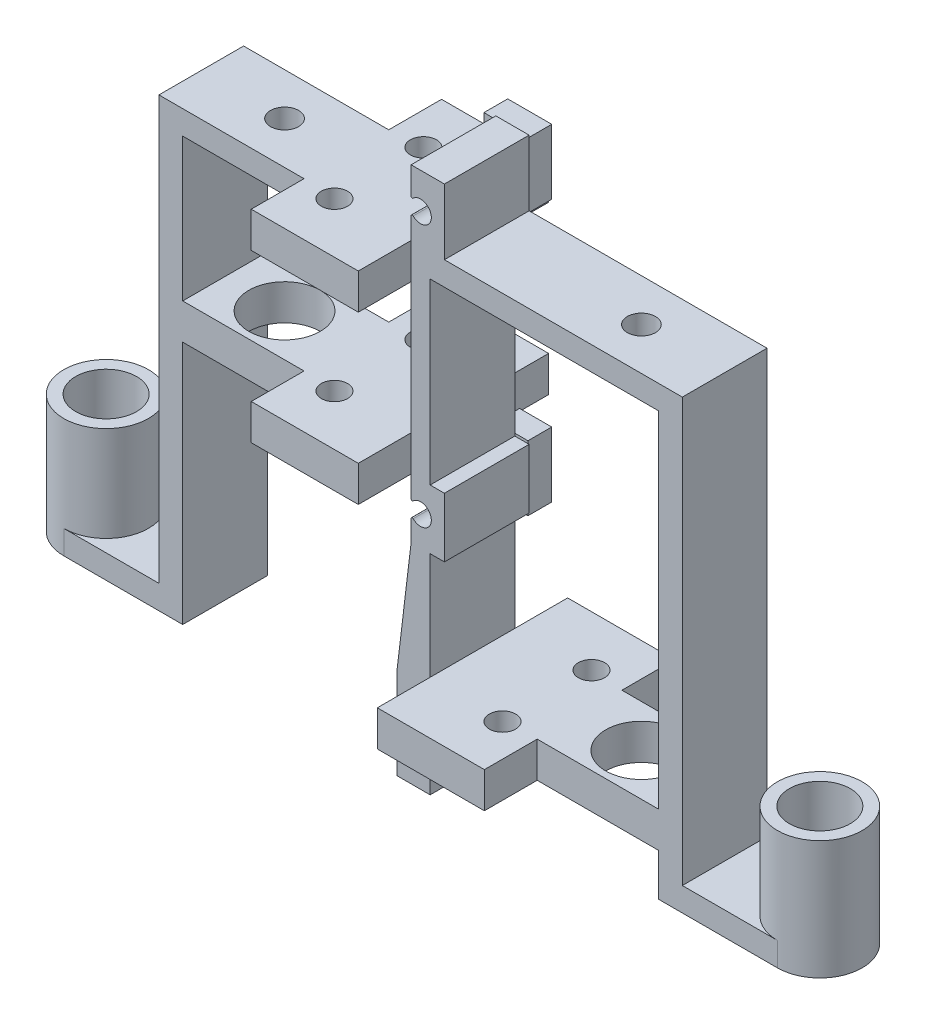
SolidWorks part; units mm, degrees
note: The reader was unsure of these and kept them because the rebuilt part matched: shared geometry of "Sketch11<3>".
material "Nylon 12 (Density Only)"
ref_plane "Front Plane" through (0, 0, 0) normal (0, 0, 1) x (1, 0, 0)
ref_plane "Top Plane" through (0, 0, 0) normal (0, 1, 0) x (1, 0, 0)
ref_plane "Right Plane" through (0, 0, 0) normal (1, 0, 0) x (0, 0, -1)
sketch "Sketch1" plane through (0, 0, 0) normal (0, 1, 0) x (1, 0, 0)
  line L0 (0, 0) -> (76.2, 0) construction
  line L1 (0, 4.5212) -> (76.2, 4.5212)
  line L2 (0, -4.5212) -> (76.2, -4.5212)
  circle A0 centre (0, 0) radius 3.2512
  circle A1 centre (76.2, 0) radius 3.2512
  arc A2 (0, 4.5212) -> (0, -4.5212) centre (0, 0) ccw
  arc A3 (76.2, -4.5212) -> (76.2, 4.5212) centre (76.2, 0) ccw
  point P5 (38.1, 0)
  point P10 (0, 3.2512)
  dimension "D1" = 76.2
  dimension "D2" = 6.5024
  dimension "D3" = 6.5024
  dimension "D4" = 1.27
extrude "Boss-Extrude1" add sketch "Sketch1" along normal blind 12.7
sketch "Sketch2" plane through (0, 12.7, 0) normal (0, 1, 0) x (1, 0, 0)
  line L2 (0, -4.5212) -> (76.2, -4.5212)
  line L3 (76.2, 4.5212) -> (0, 4.5212)
  line L4 (0, -4.5212) -> (76.2, -4.5212)
  line L5 (76.2, 4.5212) -> (0, 4.5212)
  circle A0 centre (0, 0) radius 4.5212
  circle A1 centre (0, 0) radius 3.2512
  circle A2 centre (0, 0) radius 3.2512
  circle A3 centre (76.2, 0) radius 3.2512
  circle A4 centre (76.2, 0) radius 3.2512
  circle A5 centre (76.2, 0) radius 4.5212
  arc A6 (0, 4.5212) -> (0, -4.5212) centre (0, 0) ccw
  arc A7 (76.2, -4.5212) -> (76.2, 4.5212) centre (76.2, 0) ccw
  arc A8 (0, 4.5212) -> (0, -4.5212) centre (0, 0) ccw
  arc A9 (76.2, -4.5212) -> (76.2, 4.5212) centre (76.2, 0) ccw
  dimension "D1" = 0
  dimension "D2" = 0
  dimension "D3" = 0
  dimension "D4" = 1.27
extrude "Cut-Extrude2" cut sketch "Sketch2" against normal blind 10.16 contours A5 L5 A0 L4
sketch "Sketch3" plane through (0, 2.54, 0) normal (0, 1, 0) x (1, 0, 0)
  line L0 (76.2, 4.5212) -> (0, 4.5212) construction
  line L1 (38.1, 4.5212) -> (12.7, 4.5212)
  line L2 (38.1, 4.5212) -> (38.1, -4.5212)
  line L3 (38.1, -4.5212) -> (12.7, -4.5212)
  line L4 (12.7, 4.5212) -> (12.7, -4.5212)
  line L5 (0, -4.5212) -> (76.2, -4.5212) construction
  line L7 (38.1, 4.5212) -> (63.5, 4.5212)
  line L8 (38.1, 4.5212) -> (38.1, -4.5212)
  line L9 (38.1, -4.5212) -> (63.5, -4.5212)
  line L10 (63.5, 4.5212) -> (63.5, -4.5212)
  line M4 (76.2, 4.5212) -> (0, 4.5212)
  line M6 (0, -4.5212) -> (76.2, -4.5212)
  dimension "D1" = 25.4
  dimension "D2" = 25.4
extrude "Cut-Extrude3" cut sketch "Sketch3" against normal blind 10.16 contours L4 L2 M4 M6 | L10 L2 M4 M6
sketch "Sketch4" plane through (0, 2.54, 0) normal (0, 1, 0) x (1, 0, 0)
  line L0 (0, -4.5212) -> (12.7, -4.5212) construction
  line L1 (12.7, 4.5212) -> (10.16, 4.5212)
  line L2 (12.7, 4.5212) -> (12.7, -4.5212)
  line L3 (12.7, -4.5212) -> (10.16, -4.5212)
  line L4 (10.16, 4.5212) -> (10.16, -4.5212)
  line L5 (63.5, -4.5212) -> (76.2, -4.5212) construction
  line L6 (63.5, 4.5212) -> (66.04, 4.5212)
  line L7 (63.5, 4.5212) -> (63.5, -4.5212)
  line L8 (63.5, -4.5212) -> (66.04, -4.5212)
  line L9 (66.04, 4.5212) -> (66.04, -4.5212)
  dimension "D1" = 2.54
  dimension "D2" = 2.54
extrude "Boss-Extrude2" add sketch "Sketch4" along normal blind 45.16
sketch "Sketch5" plane through (0, 47.7, 0) normal (0, 1, 0) x (1, 0, 0)
  line L0 (10.16, 4.5212) -> (66.04, -4.5212) construction
  line L1 (10.16, 4.5212) -> (66.04, 4.5212)
  line L2 (10.16, 4.5212) -> (10.16, -4.5212)
  line L3 (10.16, -4.5212) -> (66.04, -4.5212)
  line L4 (66.04, 4.5212) -> (66.04, -4.5212)
  line L5 (38.1, 0) -> (19.05, 0) construction
  line L6 (38.1, 0) -> (57.15, 0) construction
  circle A0 centre (19.05, 0) radius 1.5
  circle A1 centre (57.15, 0) radius 1.5
  dimension "D1" = 19.05
  dimension "D3" = 3
  dimension "D4" = 3
  dimension "D2" = 19.05
extrude "Boss-Extrude3" add sketch "Sketch5" against normal blind 2.54
sketch "Sketch7" plane through (0, 47.7, 0) normal (0, 1, 0) x (1, 0, 0)
  line L1 (38.1, 4.5212) -> (35.56, 4.5212)
  line L2 (38.1, 4.5212) -> (38.1, -4.5212)
  line L3 (38.1, -4.5212) -> (35.56, -4.5212)
  line L4 (10.16, -4.5212) -> (66.04, -4.5212)
  line L5 (66.04, -4.5212) -> (66.04, 4.5212)
  line L6 (66.04, 4.5212) -> (10.16, 4.5212)
  line L7 (10.16, 4.5212) -> (10.16, -4.5212)
  line L8 (10.16, -4.5212) -> (66.04, -4.5212)
  line L9 (66.04, -4.5212) -> (66.04, 4.5212)
  line L10 (66.04, 4.5212) -> (10.16, 4.5212)
  line L11 (10.16, 4.5212) -> (10.16, -4.5212)
  line L12 (35.56, 4.5212) -> (35.56, -4.5212)
  line L13 (38.1, 4.5212) -> (40.64, 4.5212)
  line L14 (38.1, 4.5212) -> (38.1, -4.5212)
  line L15 (38.1, -4.5212) -> (40.64, -4.5212)
  line L16 (40.64, 4.5212) -> (40.64, -4.5212)
  line M8 (10.16, -4.5212) -> (66.04, -4.5212)
  line M10 (66.04, 4.5212) -> (10.16, 4.5212)
  dimension "D2" = 2.54
  dimension "D3" = 2.54
  dimension "D1" = 0
extrude "Boss-Extrude4" add sketch "Sketch7" along normal blind 7 and the other way offset from surface (50.24 mm away) 2.54 contours L12 L2 M10 M8 | L16 L10 L2 M8 other way up to face at (5.2197, 0, 0)
sketch "Sketch9" plane through (0, 54.7, 0) normal (0, 1, 0) x (1, 0, 0)
  line L0 (38.1, 4.5212) -> (38.1, -4.5212) construction
  line L1 (40.64, 4.5212) -> (35.56, 4.5212) construction
  line L2 (35.56, -4.5212) -> (40.64, -4.5212) construction
  line L3 (38.1, 0) -> (29.13, 0) construction
  line L4 (37.084, 10.16) -> (25.654, 10.16)
  line L5 (37.084, 10.16) -> (37.084, -10.16)
  line L6 (37.084, -10.16) -> (25.654, -10.16)
  line L7 (25.654, 10.16) -> (25.654, -10.16)
  line L8 (39.116, 10.16) -> (50.546, 10.16)
  line L9 (39.116, 10.16) -> (39.116, -10.16)
  line L10 (39.116, -10.16) -> (50.546, -10.16)
  line L11 (50.546, 10.16) -> (50.546, -10.16)
  line L12 (38.1, 0) -> (47.07, 0) construction
  line L13 (29.13, 4.75) -> (29.13, -4.75) construction
  line L14 (29.13, 4.75) -> (29.13, 4.25) construction
  line L15 (47.07, 4.75) -> (47.07, -4.75) construction
  line L16 (29.13, 4.25) -> (37.084, 4.25) construction
  line L18 (37.084, 4.25) -> (39.116, 4.25)
  line L19 (37.084, 4.25) -> (37.084, 2.25)
  line L20 (37.084, 2.25) -> (39.116, 2.25)
  line L21 (39.116, 4.25) -> (39.116, 2.25)
  circle A0 centre (29.13, 4.75) radius 1.4
  circle A1 centre (47.07, 4.75) radius 1.4
  circle A2 centre (47.07, -4.75) radius 1.4
  circle A3 centre (29.13, -4.75) radius 1.4
  point P14 (38.1, 0)
  point P15 (39.116, 0)
  point P16 (37.084, 0)
  point P23 (29.13, 0)
  point P27 (47.07, 0)
  point P37 (37.084, 2.7631)
  point P38 (29.13, 4.25)
  dimension "D11" = 2.8
  dimension "D12" = 2.8
  dimension "D13" = 2.8
  dimension "D14" = 2.8
  dimension "D1" = 20.32
  dimension "D2" = 20.32
  dimension "D3" = 1.016
  dimension "D4" = 1.016
  dimension "D5" = 11.43
  dimension "D6" = 11.43
  dimension "D7" = 8.97
  dimension "D8" = 8.97
  dimension "D9" = 9.5
  dimension "D10" = 9.5
  dimension "D15" = 2
  dimension "D16" = 0.5
sketch "Sketch10" plane through (0, 47.7, 0) normal (0, 1, 0) x (1, 0, 0)
  line L0 (37.084, 10.16) -> (37.084, -10.16) construction
  line L1 (37.084, -10.16) -> (25.654, -10.16) construction
  line L2 (25.654, 10.16) -> (25.654, -10.16) construction
  line L3 (37.084, 10.16) -> (25.654, 10.16) construction
  line L4 (37.084, 10.16) -> (37.084, -10.16)
  line L5 (37.084, -10.16) -> (25.654, -10.16)
  line L6 (25.654, 10.16) -> (25.654, -10.16)
  line L7 (37.084, 10.16) -> (25.654, 10.16)
  circle A0 centre (29.13, -4.75) radius 1.4 construction
  circle A1 centre (29.13, 4.75) radius 1.4 construction
  circle A2 centre (29.13, -4.75) radius 1.4
  circle A3 centre (29.13, 4.75) radius 1.4
extrude "Boss-Extrude6" add sketch "Sketch10" against normal blind 21.59
sketch "Sketch11" plane through (0, 47.7, 0) normal (0, 1, 0) x (1, 0, 0)
  line L0 (37.084, 10.16) -> (37.084, -10.16) construction
  line L1 (25.654, 10.16) -> (25.654, -10.16) construction
  line L2 (37.084, 10.16) -> (37.084, -10.16)
  line L3 (25.654, 10.16) -> (25.654, -10.16)
  line L12 (10.16, -4.5212) -> (25.654, -4.5212)
  line L13 (25.654, -4.5212) -> (25.654, -10.16)
  line L14 (25.654, -10.16) -> (37.084, -10.16)
  line L15 (37.084, -10.16) -> (37.084, -4.5212)
  line L16 (37.084, -4.5212) -> (35.56, -4.5212)
  line L17 (35.56, -4.5212) -> (35.56, 4.5212)
  line L18 (35.56, 4.5212) -> (37.084, 4.5212)
  line L19 (37.084, 4.5212) -> (37.084, 10.16)
  line L20 (37.084, 10.16) -> (25.654, 10.16)
  line L21 (25.654, 10.16) -> (25.654, 4.5212)
  line L22 (25.654, 4.5212) -> (10.16, 4.5212)
  line L23 (10.16, 4.5212) -> (10.16, -4.5212)
  line L24 (10.16, -4.5212) -> (25.654, -4.5212)
  line L25 (25.654, -4.5212) -> (25.654, -10.16)
  line L26 (25.654, -10.16) -> (37.084, -10.16)
  line L27 (37.084, -10.16) -> (37.084, -4.5212)
  line L28 (37.084, -4.5212) -> (35.56, -4.5212)
  line L29 (35.56, -4.5212) -> (35.56, 4.5212)
  line L30 (35.56, 4.5212) -> (37.084, 4.5212)
  line L31 (37.084, 4.5212) -> (37.084, 10.16)
  line L32 (37.084, 10.16) -> (25.654, 10.16)
  line L33 (25.654, 10.16) -> (25.654, 4.5212)
  line L34 (25.654, 4.5212) -> (10.16, 4.5212)
  line L35 (10.16, 4.5212) -> (10.16, -4.5212)
  circle A0 centre (29.13, -4.75) radius 1.4 construction
  circle A1 centre (29.13, 4.75) radius 1.4 construction
  circle A2 centre (29.13, -4.75) radius 1.4
  circle A3 centre (29.13, 4.75) radius 1.4
  arc M13 (30.5112, -4.5212) -> (27.7488, -4.5212) centre (29.13, -4.75) cw
  line M14 (27.7488, -4.5212) -> (30.5112, -4.5212)
  arc M15 (27.7488, 4.5212) -> (30.5112, 4.5212) centre (29.13, 4.75) cw
  line M16 (30.5112, 4.5212) -> (27.7488, 4.5212)
  line M18 (25.654, -4.5212) -> (25.654, -10.16)
  line M19 (25.654, -10.16) -> (37.084, -10.16)
  line M20 (37.084, -10.16) -> (37.084, -4.5212)
  line M21 (37.084, -4.5212) -> (35.56, -4.5212)
  line M22 (35.56, -4.5212) -> (35.56, 4.5212)
  line M23 (35.56, 4.5212) -> (37.084, 4.5212)
  line M24 (37.084, 4.5212) -> (37.084, 10.16)
  line M25 (37.084, 10.16) -> (25.654, 10.16)
  line M26 (25.654, 10.16) -> (25.654, 4.5212)
  dimension "D1" = 0
extrude "Cut-Extrude4" cut sketch "Sketch11" along normal blind 7 contours L3 A3 A2 M26 M18 M19 M20 M21 M22 M23 M24 M25 M15 M13 | L2 M23 M22 M21
extrude "Cut-Extrude5" cut sketch "Sketch11<3>" against normal blind 7 contours M13 M14 | A3 M16 | M15 M16 | A2 M14
sketch "Sketch11<3>" plane through (0, 47.7, 0) normal (0, 1, 0) x (1, 0, 0) same geometry as "Sketch11"
sketch "Sketch12" plane through (0, 45.16, 0) normal (0, -1, 0) x (1, 0, 0)
  line L0 (39.116, -10.16) -> (50.546, -10.16) construction
  line L1 (50.546, -10.16) -> (50.546, 10.16) construction
  line L2 (39.116, 10.16) -> (50.546, 10.16) construction
  line L3 (39.116, -10.16) -> (39.116, 10.16) construction
  line L4 (39.116, -10.16) -> (50.546, -10.16)
  line L5 (50.546, -10.16) -> (50.546, 10.16)
  line L6 (39.116, 10.16) -> (50.546, 10.16)
  line L7 (39.116, -10.16) -> (39.116, 10.16)
  circle A0 centre (47.07, -4.75) radius 1.4 construction
  circle A1 centre (47.07, 4.75) radius 1.4 construction
  circle A2 centre (47.07, -4.75) radius 1.4
  circle A3 centre (47.07, 4.75) radius 1.4
extrude "Boss-Extrude7" add sketch "Sketch12" along normal blind 40.64
sketch "Sketch13" plane through (0, 0, 10.16) normal (0, 0, 1) x (1, 0, 0)
  line L0 (50.546, 45.16) -> (39.116, 45.16) construction
  line L1 (39.116, 45.16) -> (39.116, 4.52) construction
  line L2 (39.116, 4.52) -> (50.546, 4.52) construction
  line L3 (50.546, 4.52) -> (50.546, 45.16) construction
  line L4 (37.084, 47.7) -> (25.654, 47.7) construction
  line L5 (25.654, 47.7) -> (25.654, 26.11) construction
  line L6 (25.654, 26.11) -> (37.084, 26.11) construction
  line L7 (37.084, 26.11) -> (37.084, 47.7) construction
  line L8 (50.546, 45.16) -> (39.116, 45.16)
  line L9 (39.116, 45.16) -> (39.116, 4.52)
  line L10 (39.116, 4.52) -> (50.546, 4.52)
  line L11 (50.546, 4.52) -> (50.546, 45.16)
  line L12 (37.084, 47.7) -> (25.654, 47.7)
  line L13 (25.654, 47.7) -> (25.654, 26.11)
  line L14 (25.654, 26.11) -> (37.084, 26.11)
  line L15 (37.084, 26.11) -> (37.084, 47.7)
  line L16 (25.654, 29.92) -> (37.084, 29.92)
  line L17 (37.084, 43.89) -> (25.654, 43.89)
  line L18 (39.116, 8.33) -> (50.546, 8.33)
  line M3 (50.546, 45.16) -> (39.116, 45.16)
  line M4 (39.116, 45.16) -> (39.116, 4.52)
  dimension "D1" = 3.81
  dimension "D2" = 3.81
extrude "Cut-Extrude6" cut sketch "Sketch13" against normal through all contours L15 L17 L13 L16 | L18 L11 M4 M3
sketch "Sketch15" plane through (12.7, 0, 0) normal (1, 0, 0) x (0, 0, -1)
  line L0 (10.16, 29.92) -> (4.5212, 29.92) construction
  line L1 (4.5212, 29.92) -> (4.5212, 26.11) construction
  line L2 (4.5212, 26.11) -> (10.16, 26.11) construction
  line L3 (10.16, 26.11) -> (10.16, 29.92) construction
  line L4 (-4.5212, 29.92) -> (-10.16, 29.92) construction
  line L5 (-10.16, 29.92) -> (-10.16, 26.11) construction
  line L6 (-10.16, 26.11) -> (-4.5212, 26.11) construction
  line L7 (-4.5212, 26.11) -> (-4.5212, 29.92) construction
  line L8 (10.16, 29.92) -> (4.5212, 29.92)
  line L9 (4.5212, 29.92) -> (4.5212, 26.11)
  line L10 (4.5212, 26.11) -> (10.16, 26.11)
  line L11 (10.16, 26.11) -> (10.16, 29.92)
  line L12 (-4.5212, 29.92) -> (-10.16, 29.92)
  line L13 (-10.16, 29.92) -> (-10.16, 26.11)
  line L14 (-10.16, 26.11) -> (-4.5212, 26.11)
  line L15 (-4.5212, 26.11) -> (-4.5212, 29.92)
  line L17 (-4.5212, 29.92) -> (4.5212, 29.92)
  line L18 (-4.5212, 29.92) -> (-4.5212, 26.11)
  line L19 (-4.5212, 26.11) -> (4.5212, 26.11)
  line L20 (4.5212, 29.92) -> (4.5212, 26.11)
  line M1 (4.5212, 0) -> (4.5212, 45.16)
  line M3 (-4.5212, 45.16) -> (-4.5212, 0)
extrude "Boss-Extrude8" add sketch "Sketch15" along normal up to surface (12.954 mm away) contours L19 L17 M3 M1 up to face at (25.654, 28.015, 0)
sketch "Sketch16" plane through (63.5, 0, 0) normal (-1, 0, 0) x (0, 0, 1)
  line L0 (4.5212, 47.7) -> (-4.5212, 47.7) construction
  line L1 (-4.5212, 47.7) -> (-4.5212, 2.54) construction
  line L2 (-4.5212, 2.54) -> (4.5212, 2.54) construction
  line L3 (4.5212, 2.54) -> (4.5212, 47.7) construction
  line L4 (10.16, 4.52) -> (10.16, 8.33) construction
  line L5 (10.16, 8.33) -> (4.5212, 8.33) construction
  line L6 (4.5212, 8.33) -> (4.5212, 4.52) construction
  line L7 (4.5212, 4.52) -> (10.16, 4.52) construction
  line L8 (-4.5212, 4.52) -> (-4.5212, 8.33) construction
  line L9 (-4.5212, 8.33) -> (-10.16, 8.33) construction
  line L10 (-10.16, 8.33) -> (-10.16, 4.52) construction
  line L11 (-10.16, 4.52) -> (-4.5212, 4.52) construction
  line L12 (4.5212, 47.7) -> (-4.5212, 47.7)
  line L13 (-4.5212, 47.7) -> (-4.5212, 2.54)
  line L14 (-4.5212, 2.54) -> (4.5212, 2.54)
  line L15 (4.5212, 2.54) -> (4.5212, 47.7)
  line L16 (10.16, 4.52) -> (10.16, 8.33)
  line L17 (10.16, 8.33) -> (4.5212, 8.33)
  line L18 (4.5212, 8.33) -> (4.5212, 4.52)
  line L19 (4.5212, 4.52) -> (10.16, 4.52)
  line L20 (-4.5212, 4.52) -> (-4.5212, 8.33)
  line L21 (-4.5212, 8.33) -> (-10.16, 8.33)
  line L22 (-10.16, 8.33) -> (-10.16, 4.52)
  line L23 (-10.16, 4.52) -> (-4.5212, 4.52)
  line L25 (-4.5212, 8.33) -> (4.5212, 8.33)
  line L26 (-4.5212, 8.33) -> (-4.5212, 4.52)
  line L27 (-4.5212, 4.52) -> (4.5212, 4.52)
  line L28 (4.5212, 8.33) -> (4.5212, 4.52)
extrude "Boss-Extrude9" add sketch "Sketch16" along normal up to surface (12.954 mm away) contours L13 L27 L15 L25 up to face at (50.546, 6.425, 0)
sketch "Sketch17" plane through (0, 0, 4.5212) normal (0, 0, 1) x (1, 0, 0)
  line L0 (37.084, 26.11) -> (37.084, 19.76)
  line L1 (37.084, 19.76) -> (35.56, 7.06)
  line L2 (35.56, -2.54) -> (35.56, 26.11) construction
  line M23 (37.084, 26.11) -> (35.56, 26.11)
  line M24 (35.56, 26.11) -> (35.56, -2.54)
  dimension "D1" = 6.35
  dimension "D2" = 12.7
extrude "Cut-Extrude7" cut sketch "Sketch17" against normal through all and the other way through all contours L1 L0 M23 M24
sketch "Sketch18" plane through (0, 0, 4.5212) normal (0, 0, 1) x (1, 0, 0)
  line L0 (40.64, 47.7) -> (40.64, 54.7) construction
  line L1 (37.084, 26.11) -> (40.64, 26.11)
  line L2 (37.084, 26.11) -> (37.084, 19.76)
  line L3 (37.084, 19.76) -> (40.64, 19.76)
  line L4 (40.64, 26.11) -> (40.64, 19.76)
extrude "Boss-Extrude10" add sketch "Sketch18" against normal up to surface (9.0424 mm away) up to face at (48.5242, 20.5052, -4.5212)
sketch "Sketch19" plane through (0, 0, 4.5212) normal (0, 0, 1) x (1, 0, 0)
  line L0 (38.1, -2.54) -> (38.1, 54.7) construction
  line L1 (40.64, -2.54) -> (35.56, -2.54) construction
  line L2 (25.654, 26.11) -> (37.084, 26.11) construction
  line L3 (50.546, 4.52) -> (39.116, 4.52) construction
  line L4 (25.654, 47.7) -> (37.084, 47.7) construction
  circle A0 centre (38.1, 50.9) radius 1.143
  circle A1 centre (38.1, 1.32) radius 1.143
  circle A2 centre (38.1, 22.91) radius 1.143
  dimension "D1" = 2.286
  dimension "D2" = 3.2
  dimension "D3" = 3.2
  dimension "D4" = 3.2
sketch "Sketch21" plane through (0, 4.52, 0) normal (0, -1, 0) x (1, 0, 0)
  circle A0 centre (57.15, 0) radius 1.5 construction
  circle A1 centre (19.05, 0) radius 1.5 construction
  circle A2 centre (57.15, 0) radius 1.5
  circle A3 centre (19.05, 0) radius 1.5
  circle A4 centre (57.15, 0) radius 3.81
  circle A5 centre (19.05, 0) radius 3.81
  dimension "D1" = 7.62
  dimension "D2" = 7.62
extrude "Cut-Extrude8" cut sketch "Sketch21" against normal up to surface (40.64 mm away) contours A4 A2 | A2 | A3 | A5 A3 up to face at (19.05, 45.16, 1.5)
extrude "Cut-Extrude9" cut sketch "Sketch19" against normal blind 12.7
sketch "Sketch22" plane through (0, 0, 4.5212) normal (0, 0, 1) x (1, 0, 0)
  line L0 (39.116, 4.52) -> (40.64, 4.52) construction
  line L1 (40.64, -2.54) -> (39.116, -2.54)
  line L2 (40.64, -2.54) -> (40.64, 4.52)
  line L3 (40.64, 4.52) -> (39.116, 4.52)
  line L4 (39.116, -2.54) -> (39.116, 4.52)
  point P7 (39.116, 4.52)
extrude "Cut-Extrude10" cut sketch "Sketch22" against normal through all both and the other way through all
fillet "Fillet1" radius 0.127 6 edges at (37.084, 50.3764, 0) (37.084, 51.4236, 0) (37.084, 22.3864, 0) (37.084, 23.4336, 0) (39.116, 0.7964, 0) (39.116, 1.8436, 0)
ref_plane "Plane1" through (0, 0, -2.25) normal (0, 0, -1) x (-1, 0, 0)
sketch "Sketch23" plane through (0, 0, -2.25) normal (0, 0, -1) x (-1, 0, 0)
  line L0 (-66.04, 47.7) -> (-40.64, 47.7) construction
  line L1 (-37.084, 54.7) -> (-40.64, 54.7)
  line L2 (-37.084, 54.7) -> (-37.084, 47.7)
  line L3 (-37.084, 47.7) -> (-40.64, 47.7)
  line L4 (-40.64, 54.7) -> (-40.64, 47.7)
  line L5 (-40.64, 47.7) -> (-40.64, 54.7) construction
  line L6 (-39.116, 4.52) -> (-50.546, 4.52) construction
  line L7 (-40.64, 19.76) -> (-37.084, 19.76)
  line L8 (-40.64, 19.76) -> (-40.64, 26.11)
  line L9 (-40.64, 26.11) -> (-37.084, 26.11)
  line L10 (-37.084, 19.76) -> (-37.084, 26.11)
  line L11 (-39.116, 4.52) -> (-35.56, 4.52)
  line L12 (-39.116, 4.52) -> (-39.116, -2.54)
  line L13 (-39.116, -2.54) -> (-35.56, -2.54)
  line L14 (-35.56, 4.52) -> (-35.56, -2.54)
  line L15 (-39.116, 3.52) -> (-36.957, 3.52)
  line L16 (-39.116, 3.52) -> (-39.116, -0.88)
  line L17 (-39.116, -0.88) -> (-36.957, -0.88)
  line L18 (-36.957, 3.52) -> (-36.957, -0.88)
  line L19 (-37.084, 25.11) -> (-39.243, 25.11)
  line L20 (-37.084, 25.11) -> (-37.084, 20.71)
  line L21 (-37.084, 20.71) -> (-39.243, 20.71)
  line L22 (-39.243, 25.11) -> (-39.243, 20.71)
  line L23 (-37.084, 53.1) -> (-39.243, 53.1)
  line L24 (-37.084, 53.1) -> (-37.084, 48.7)
  line L25 (-37.084, 48.7) -> (-39.243, 48.7)
  line L26 (-39.243, 53.1) -> (-39.243, 48.7)
  line L27 (-37.084, 26.11) -> (-25.654, 26.11) construction
  line L28 (-25.654, 47.7) -> (-37.084, 47.7) construction
  arc A48 (-37.2999, 51.7163) -> (-37.2999, 50.0837) centre (-38.1, 50.9) ccw construction
  arc A49 (-37.2999, 23.7263) -> (-37.2999, 22.0937) centre (-38.1, 22.91) ccw construction
  arc A50 (-38.9001, 0.5037) -> (-38.9001, 2.1363) centre (-38.1, 1.32) ccw construction
  dimension "D1" = 1
  dimension "D2" = 4.4
  dimension "D3" = 1
  dimension "D4" = 4.4
  dimension "D5" = 1
  dimension "D6" = 4.4
extrude "Cut-Extrude11" cut sketch "Sketch23" along normal up to surface (2.2712 mm away) and the other way blind 0.5 contours L23 L26 L25 L2 | L19 L22 L21 L10 | L18 L15 L12 L17 up to face at (44.6476, 22.5093, -4.5212)
sketch "Sketch24" plane through (0, 0, -4.5212) normal (0, 0, -1) x (-1, 0, 0)
  line L0 (-37.0456, 19.44) -> (-40.513, 19.44)
  line L1 (-40.513, 19.44) -> (-40.513, 26.38)
  line L2 (-40.513, 26.38) -> (-37.084, 26.38)
  line L3 (-39.116, 4.79) -> (-35.687, 4.79)
  line L4 (-35.687, 4.79) -> (-35.687, -2.15)
  line L5 (-35.687, -2.15) -> (-39.116, -2.15)
  line L6 (-37.084, 47.43) -> (-40.513, 47.43)
  line L7 (-40.513, 47.43) -> (-40.513, 54.37)
  line L8 (-40.513, 54.37) -> (-37.084, 54.37)
  line L9 (-37.084, 19.44) -> (-40.513, 19.44) construction
  line L10 (-37.0456, 26.38) -> (-40.513, 26.38)
  line L11 (-39.116, -2.15) -> (-40.386, -2.15)
  line L12 (-39.116, -2.15) -> (-39.116, 4.79)
  line L13 (-39.116, 4.79) -> (-40.386, 4.79)
  line L14 (-40.386, -2.15) -> (-40.386, 4.79)
  line L15 (-37.0456, 19.44) -> (-35.7756, 19.44)
  line L16 (-37.0456, 19.44) -> (-37.0456, 26.38)
  line L17 (-37.0456, 26.38) -> (-35.7756, 26.38)
  line L18 (-35.7756, 19.44) -> (-35.7756, 26.38)
  line L19 (-37.084, 47.43) -> (-35.814, 47.43)
  line L20 (-37.084, 47.43) -> (-37.084, 54.37)
  line L21 (-37.084, 54.37) -> (-35.814, 54.37)
  line L22 (-35.814, 47.43) -> (-35.814, 54.37)
  line L40 (-39.243, 48.7) -> (-39.243, 53.1)
  line L41 (-39.243, 53.1) -> (-37.084, 53.1)
  line L42 (-37.084, 53.1) -> (-37.084, 54.7)
  line L43 (-37.084, 54.7) -> (-40.64, 54.7)
  line L44 (-40.64, 54.7) -> (-40.64, 47.7)
  line L45 (-40.64, 47.7) -> (-66.04, 47.7)
  line L46 (-66.04, 47.7) -> (-66.04, 2.54)
  line L47 (-66.04, 2.54) -> (-76.2, 2.54)
  line L48 (-76.2, 2.54) -> (-76.2, 0)
  line L49 (-76.2, 0) -> (-63.5, 0)
  line L50 (-63.5, 0) -> (-63.5, 4.52)
  line L51 (-63.5, 4.52) -> (-50.546, 4.52)
  line L52 (-50.546, 4.52) -> (-50.546, 8.33)
  line L53 (-50.546, 8.33) -> (-63.5, 8.33)
  line L54 (-63.5, 8.33) -> (-63.5, 45.16)
  line L55 (-63.5, 45.16) -> (-39.116, 45.16)
  line L56 (-39.116, 45.16) -> (-39.116, 26.11)
  line L57 (-39.116, 26.11) -> (-40.64, 26.11)
  line L58 (-40.64, 26.11) -> (-40.64, 19.76)
  line L59 (-40.64, 19.76) -> (-39.116, 19.76)
  line L60 (-39.116, 19.76) -> (-39.116, 8.33)
  line L61 (-39.116, 8.33) -> (-39.116, 4.52)
  line L62 (-39.116, 4.52) -> (-39.116, 3.52)
  line L63 (-39.116, 3.52) -> (-36.957, 3.52)
  line L64 (-36.957, 3.52) -> (-36.957, -0.88)
  line L65 (-36.957, -0.88) -> (-39.116, -0.88)
  line L66 (-39.116, -0.88) -> (-39.116, -2.54)
  line L67 (-39.116, -2.54) -> (-35.56, -2.54)
  line L68 (-35.56, -2.54) -> (-35.56, 7.06)
  line L69 (-35.56, 7.06) -> (-37.084, 19.76)
  line L70 (-37.084, 19.76) -> (-37.084, 20.71)
  line L71 (-37.084, 20.71) -> (-39.243, 20.71)
  line L72 (-39.243, 20.71) -> (-39.243, 25.11)
  line L73 (-39.243, 25.11) -> (-37.084, 25.11)
  line L74 (-37.084, 25.11) -> (-37.084, 26.11)
  line L75 (-37.084, 26.11) -> (-37.084, 29.92)
  line L76 (-37.084, 29.92) -> (-37.084, 43.89)
  line L77 (-37.084, 43.89) -> (-37.084, 47.7)
  line L78 (-37.084, 47.7) -> (-37.084, 48.7)
  line L79 (-37.084, 48.7) -> (-39.243, 48.7)
  line L80 (-39.243, 48.7) -> (-39.243, 53.1)
  line L81 (-39.243, 53.1) -> (-37.084, 53.1)
  line L82 (-37.084, 53.1) -> (-37.084, 54.7)
  line L83 (-37.084, 54.7) -> (-40.64, 54.7)
  line L84 (-40.64, 54.7) -> (-40.64, 47.7)
  line L85 (-40.64, 47.7) -> (-66.04, 47.7)
  line L86 (-66.04, 47.7) -> (-66.04, 2.54)
  line L87 (-66.04, 2.54) -> (-76.2, 2.54)
  line L88 (-76.2, 2.54) -> (-76.2, 0)
  line L89 (-76.2, 0) -> (-63.5, 0)
  line L90 (-63.5, 0) -> (-63.5, 4.52)
  line L91 (-63.5, 4.52) -> (-50.546, 4.52)
  line L92 (-50.546, 4.52) -> (-50.546, 8.33)
  line L93 (-50.546, 8.33) -> (-63.5, 8.33)
  line L94 (-63.5, 8.33) -> (-63.5, 45.16)
  line L95 (-63.5, 45.16) -> (-39.116, 45.16)
  line L96 (-39.116, 45.16) -> (-39.116, 26.11)
  line L97 (-39.116, 26.11) -> (-40.64, 26.11)
  line L98 (-40.64, 26.11) -> (-40.64, 19.76)
  line L99 (-40.64, 19.76) -> (-39.116, 19.76)
  line L100 (-39.116, 19.76) -> (-39.116, 8.33)
  line L101 (-39.116, 8.33) -> (-39.116, 4.52)
  line L102 (-39.116, 4.52) -> (-39.116, 3.52)
  line L103 (-39.116, 3.52) -> (-36.957, 3.52)
  line L104 (-36.957, 3.52) -> (-36.957, -0.88)
  line L105 (-36.957, -0.88) -> (-39.116, -0.88)
  line L106 (-39.116, -0.88) -> (-39.116, -2.54)
  line L107 (-39.116, -2.54) -> (-35.56, -2.54)
  line L108 (-35.56, -2.54) -> (-35.56, 7.06)
  line L109 (-35.56, 7.06) -> (-37.084, 19.76)
  line L110 (-37.084, 19.76) -> (-37.084, 20.71)
  line L111 (-37.084, 20.71) -> (-39.243, 20.71)
  line L112 (-39.243, 20.71) -> (-39.243, 25.11)
  line L113 (-39.243, 25.11) -> (-37.084, 25.11)
  line L114 (-37.084, 25.11) -> (-37.084, 26.11)
  line L115 (-37.084, 26.11) -> (-37.084, 29.92)
  line L116 (-37.084, 29.92) -> (-37.084, 43.89)
  line L117 (-37.084, 43.89) -> (-37.084, 47.7)
  line L118 (-37.084, 47.7) -> (-37.084, 48.7)
  line L119 (-37.084, 48.7) -> (-39.243, 48.7)
  line M41 (-39.243, 48.7) -> (-39.243, 53.1)
  line M42 (-39.243, 53.1) -> (-37.084, 53.1)
  line M43 (-37.084, 53.1) -> (-37.084, 54.7)
  line M57 (-39.116, 45.16) -> (-39.116, 26.11)
  line M58 (-39.116, 26.11) -> (-40.64, 26.11)
  line M60 (-40.64, 19.76) -> (-39.116, 19.76)
  line M61 (-39.116, 19.76) -> (-39.116, 8.33)
  line M62 (-39.116, 8.33) -> (-39.116, 4.52)
  line M63 (-39.116, 4.52) -> (-39.116, 3.52)
  line M64 (-39.116, 3.52) -> (-36.957, 3.52)
  line M65 (-36.957, 3.52) -> (-36.957, -0.88)
  line M66 (-36.957, -0.88) -> (-39.116, -0.88)
  line M67 (-39.116, -0.88) -> (-39.116, -2.54)
  line M70 (-35.56, 7.06) -> (-37.084, 19.76)
  line M71 (-37.084, 19.76) -> (-37.084, 20.71)
  line M72 (-37.084, 20.71) -> (-39.243, 20.71)
  line M73 (-39.243, 20.71) -> (-39.243, 25.11)
  line M74 (-39.243, 25.11) -> (-37.084, 25.11)
  line M75 (-37.084, 25.11) -> (-37.084, 26.11)
  line M76 (-37.084, 26.11) -> (-37.084, 29.92)
  line M78 (-37.084, 43.89) -> (-37.084, 47.7)
  line M79 (-37.084, 47.7) -> (-37.084, 48.7)
  line M80 (-37.084, 48.7) -> (-39.243, 48.7)
  dimension "D3" = 1.27
  dimension "D1" = 0
  dimension "D2" = 1.27
extrude "Boss-Extrude11" add sketch "Sketch24" along normal blind 2.54 contours L8 L7 L6 M78 M79 M80 M41 M42 M43 | L19 L22 L21 L20 M43 M79 M78 | L20 M80 M42 M41 | L15 L18 L17 L16 | L16 L10 M70 M76 M75 M74 M73 M72 M71 | L2 L1 L0 M57 M58 M60 M61 M70 M71 M72 M73 M74 M75 M76 | L1 L0 M61 M60 | L2 L1 M58 M57 | L14 L11 L12 L13 M67 M63 M62 | L12 M66 M65 M64 | L5 L4 L3 M62 M63 M64 M65 M66 M67
sketch "Sketch25" plane through (0, 0, -7.0612) normal (0, 0, -1) x (-1, 0, 0)
  arc A0 (-37.2999, 51.7163) -> (-37.2999, 50.0837) centre (-38.1, 50.9) ccw construction
  arc A1 (-37.2999, 23.7263) -> (-37.2999, 22.0937) centre (-38.1, 22.91) ccw construction
  arc A2 (-38.9001, 0.5037) -> (-38.9001, 2.1363) centre (-38.1, 1.32) ccw construction
  arc A3 (-37.2999, 51.7163) -> (-37.2999, 50.0837) centre (-38.1, 50.9) ccw
  arc A4 (-37.2999, 23.7263) -> (-37.2999, 22.0937) centre (-38.1, 22.91) ccw
  arc A5 (-38.9001, 0.5037) -> (-38.9001, 2.1363) centre (-38.1, 1.32) ccw
  circle A6 centre (-38.1, 50.9) radius 1.143
  circle A7 centre (-38.1, 22.91) radius 1.143
  circle A8 centre (-38.1, 1.32) radius 1.143
extrude "Cut-Extrude13" cut sketch "Sketch25" against normal through all contours A5 A8 | A4 A7 | A3 A6
chamfer "Chamfer1" distance 1.016 angle 45 3 edges at (36.957, 50.9, -7.0612) (36.957, 22.91, -7.0612) (36.957, 1.32, -7.0612)
